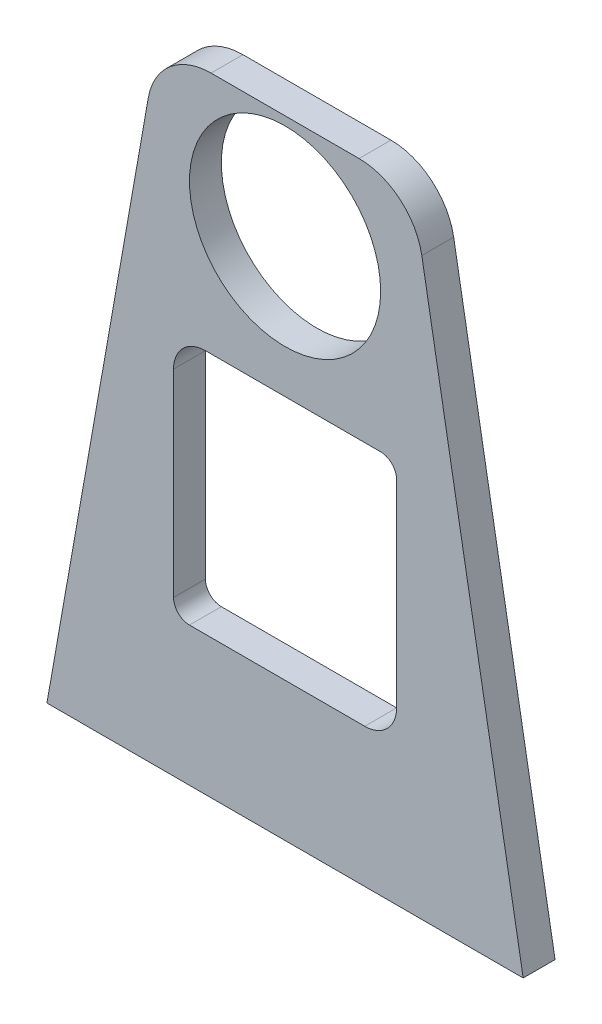
SolidWorks part; units mm, degrees
ref_plane "Front" through (0, 0, 0) normal (0, 0, 1) x (1, 0, 0)
ref_plane "Top" through (0, 0, 0) normal (0, 1, 0) x (1, 0, 0)
ref_plane "Right" through (0, 0, 0) normal (1, 0, 0) x (0, 0, -1)
sketch "Sketch3" plane through (0, 0, 0) normal (0, 0, 1) x (1, 0, 0)
  line L0 (-26.6013, 0) -> (11.3613, 0)
  line L1 (11.3613, 0) -> (3.2802, 45.8304)
  line L3 (-18.5202, 45.8304) -> (-26.6013, 0)
  line L4 (-7.62, 0) -> (-7.62, 30.6412) construction
  line L6 (-15.24, 11.0631) -> (-1.27, 11.0631)
  line L7 (-16.51, 12.3331) -> (-16.51, 28.1012)
  line L8 (-13.97, 30.6412) -> (0, 30.6412)
  line L9 (1.27, 13.6031) -> (1.27, 29.3712)
  line L10 (-16.51, 11.0631) -> (1.27, 30.6412) construction
  line L11 (-16.51, 30.6412) -> (1.27, 11.0631) construction
  line L15 (-15.24, 50.0282) -> (-15.24, 50.0689)
  line L16 (0, 50.0282) -> (0, 50.0689)
  line L17 (-13.5174, 50.0282) -> (-1.7226, 50.0282)
  arc A0 (-13.97, 30.6412) -> (-16.51, 28.1012) centre (-13.97, 28.1012) ccw
  arc A1 (1.27, 13.6031) -> (-1.27, 11.0631) centre (-1.27, 13.6031) cw
  arc A2 (0, 30.6412) -> (1.27, 29.3712) centre (0, 29.3712) cw
  arc A3 (-15.24, 11.0631) -> (-16.51, 12.3331) centre (-15.24, 12.3331) cw
  circle A9 centre (-7.62, 41.7135) radius 7.62
  arc A10 (-18.5202, 45.8304) -> (-13.5174, 50.0282) centre (-13.5174, 44.9482) cw
  arc A11 (3.2802, 45.8304) -> (-1.7226, 50.0282) centre (-1.7226, 44.9482) ccw
  point P7 (-7.62, 20.8521)
  point P28 (-17.78, 50.0282)
  point P33 (2.54, 50.0282)
  dimension "D4" = 2.54
  dimension "D5" = 2.54
  dimension "D6" = 1.27
  dimension "D7" = 1.27
  dimension "D8" = 15.24
  dimension "D9" = 5.08
  dimension "D11" = 5.08
  dimension "D1" = 80
  dimension "D2" = 80
  dimension "D3" = 50.8
  dimension "D10" = 20.32
extrude "Boss-Extrude1" add sketch "Sketch3" along normal blind 2.54 contours L3 L0 L1 L6 A3 L7 A0 L8 A2 L9 A1 region at (-21.9423, 22.8061, 0)
